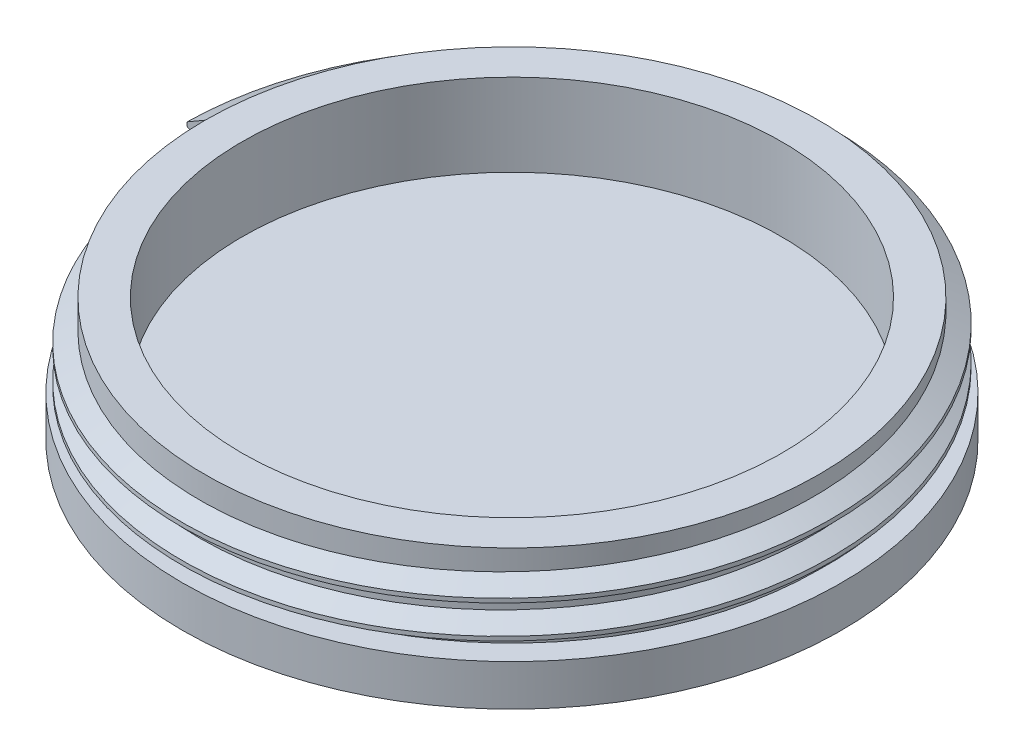
SolidWorks part; units mm, degrees
ref_plane "Front Plane" through (0, 0, 0) normal (0, 0, 1) x (1, 0, 0)
ref_plane "Top Plane" through (0, 0, 0) normal (0, 1, 0) x (1, 0, 0)
ref_plane "Right Plane" through (0, 0, 0) normal (1, 0, 0) x (0, 0, -1)
sketch "Sketch1" plane through (0, 0, 0) normal (0, 1, 0) x (1, 0, 0)
  circle A0 centre (0, 0) radius 37.25
  circle A1 centre (0, 0) radius 40
  dimension "D1" = 74.5
  dimension "D2" = 80
extrude "Boss-Extrude1" add sketch "Sketch1" against normal blind 5 contours A1
extrude "Boss-Extrude2" add sketch "Sketch1<4>" along normal blind 10 contours A0 region at (0, 0, 0)
sketch "Sketch1<4>" plane through (0, 0, 0) normal (0, 1, 0) x (1, 0, 0) same geometry as "Sketch1"
thread "Thread1" pitch 4 method extrude profile "Thread Profile1" start angle 0, offset 0, length 10, pitch 4, diameter 74.5
ref_plane "Plane1" through (-37.25, 10, 0) normal (0, 0, 1) x (-1, 0, 0)
sketch "Thread Profile1" plane through (-37.25, 10, 0) normal (0, 0, 1) x (-1, 0, 0)
  line L0 (0, 0) -> (0, 4) construction
  line L1 (0, 0) -> (2.1651, 1.25)
  line L2 (2.1651, 1.25) -> (2.1651, 1.75)
  line L3 (2.1651, 1.75) -> (0, 3)
  line L4 (2.1651, 1.5) -> (0, 1.5) construction
  line L11 (0, 0) -> (0, 3)
  point P2 (0, 0)
  dimension "Pitch" = 4
  dimension "Profile_Angle" = 60
  dimension "Profile_Land" = 0.5
  dimension "Profile_Height" = 2.1651
sketch "Sketch6" plane through (0, 10, 0) normal (0, 1, 0) x (1, 0, 0)
  circle A0 centre (0, 0) radius 32.75
  dimension "D1" = 65.5
extrude "Cut-Extrude1" cut sketch "Sketch6" against normal blind 10
